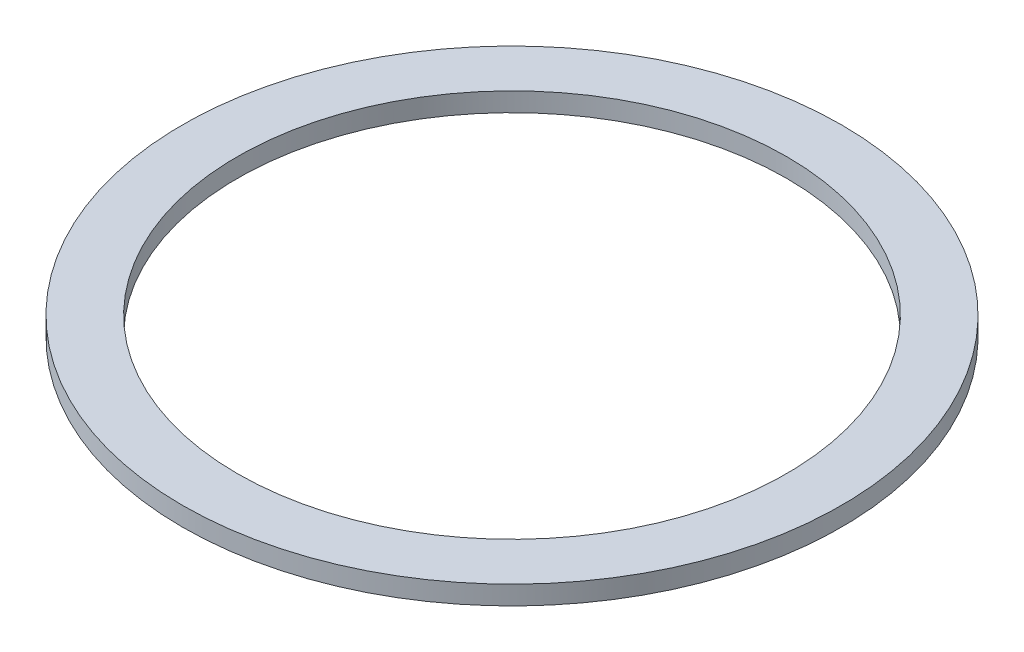
SolidWorks part; units mm, degrees
ref_plane "Front Plane" through (0, 0, 0) normal (0, 0, 1) x (1, 0, 0)
ref_plane "Top Plane" through (0, 0, 0) normal (0, 1, 0) x (1, 0, 0)
ref_plane "Right Plane" through (0, 0, 0) normal (1, 0, 0) x (0, 0, -1)
sketch "Sketch1" plane through (0, 0, 0) normal (0, 1, 0) x (1, 0, 0)
  circle A0 centre (0, 0) radius 7.5
  circle A1 centre (0, 0) radius 6.25
  dimension "D1" = 15
  dimension "D2" = 12.5
extrude "Boss-Extrude1" add sketch "Sketch1" along normal blind 0.43
